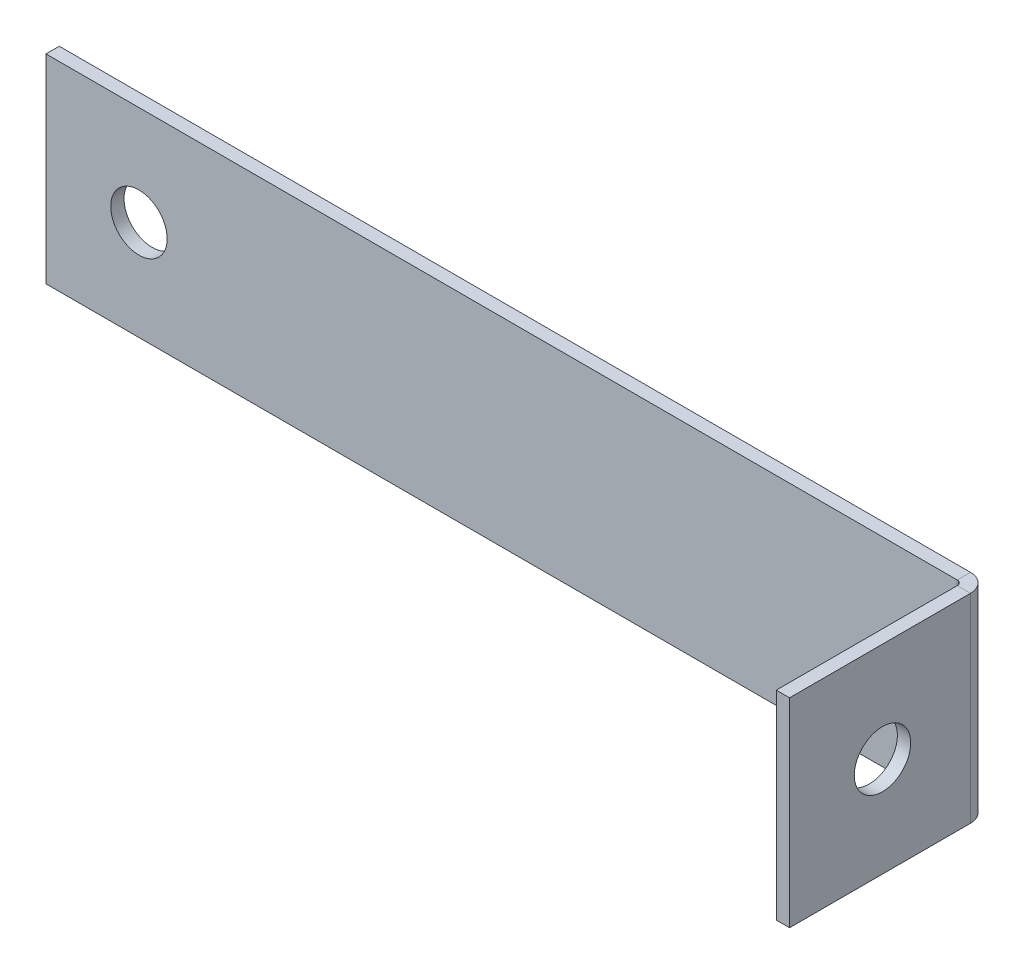
SolidWorks part; units mm, degrees
note: The reader was unsure of these and kept them because the rebuilt part matched: flange length of "Edge-Flange1".
material "Galvanized Steel"
ref_plane "Front Plane" through (0, 0, 0) normal (0, 0, 1) x (1, 0, 0)
ref_plane "Top Plane" through (0, 0, 0) normal (0, 1, 0) x (1, 0, 0)
ref_plane "Right Plane" through (0, 0, 0) normal (1, 0, 0) x (0, 0, -1)
sketch "Sketch1" plane through (0, 0, 0) normal (0, 0, 1) x (1, 0, 0)
  line L1 (60.7597, 25.5212) -> (-79.2403, 25.5212)
  line L2 (60.7597, 25.5212) -> (60.7597, -4.4788)
  line L3 (60.7597, -4.4788) -> (-79.2403, -4.4788)
  line L4 (-79.2403, 25.5212) -> (-79.2403, -4.4788)
  circle A0 centre (-65.2403, 10.5212) radius 4.25
  dimension "D3" = 8.5
  dimension "D1" = 140
  dimension "D2" = 30
  dimension "D4" = 14
base flange "Base-Flange1" sketch "Sketch1" thickness 2 reverse thickness direction no parameters "D1"=0.7366
edge flange "Edge-Flange1" sketch "Sketch8" flange angle 90 flange length 30 flange position material inside bend radius 0.7366 thickness 2 relief obround parameters "D6"=10
sketch "Sketch8" plane through (60.7597, 0, 0) normal (-1, 0, 0) x (0, -1, 0)
  line L1 (4.4788, 0) -> (-25.5212, 0) construction
  line L2 (-25.5212, 0) -> (-25.5212, 28)
  line L3 (-25.5212, 28) -> (4.4788, 28)
  line L4 (4.4788, 28) -> (4.4788, 0)
  line L5 (4.4788, 0) -> (-25.5212, 0)
bend "EdgeBend1" bend radius 0.7366 bend angle 90 parameters "D5"=1
sketch "Sketch9" plane through (60.7597, 0, 0) normal (1, 0, 0) x (0, 0, -1)
  circle A0 centre (-14, 10.5212) radius 4.25
  dimension "D1" = 8.5
extrude "Cut-Extrude1" cut sketch "Sketch9" against normal blind 10 normal cut yes
sketch "Bend-Lines1" [suppressed] plane through (0, 0, 0) normal (0, 1, 0) x (1, 0, 0)
sketch "Bounding-Box1" [suppressed] plane through (0, 0, 0) normal (0, 1, 0) x (1, 0, 0)
sheet metal parameters "Sheet-Metal1" thickness 2 parameters "D1"=0.7366
flat pattern "Flat-Pattern1" [suppressed]
sketch "Bend-Lines2" plane through (0, 0, 0) normal (0, 1, 0) x (1, 0, 0)
sketch3d "Bounding-Box2" [suppressed]
  line L0 (79.2403, -4.4788, 0) -> (-50.7597, -4.4788, 0) construction
  line L1 (79.2403, 25.5212, 0) -> (-50.7597, 25.5212, 0) construction
  line L2 (79.2403, -4.4788, 0) -> (79.2403, 25.5212, 0) construction
  line L3 (-50.7597, -4.4788, 0) -> (-50.7597, 25.5212, 0) construction
sheet metal parameters "Sheet-Metal2" thickness 2 parameters "D1"=0.7366
flat pattern "Flat-Pattern1"
sketch "Bend-Lines2" plane through (0, 0, 0) normal (0, 0, 1) x (1, 0, 0)
  line L0 (49.387, -4.4788) -> (49.387, 25.5212) construction
  line L1 (49.387, -4.4788) -> (49.387, 25.5212) construction
sketch3d "Bounding-Box2" [suppressed]
  line L0 (-79.2403, -4.4788, 0) -> (78.0144, -4.4788, 0) construction
  line L1 (-79.2403, 25.5212, 0) -> (78.0144, 25.5212, 0) construction
  line L2 (-79.2403, -4.4788, 0) -> (-79.2403, 25.5212, 0) construction
  line L3 (78.0144, -4.4788, 0) -> (78.0144, 25.5212, 0) construction
bend of the flat pattern "Flatten-<EdgeBend1>1"
sheet metal parameters "Sheet-Metal3" thickness 2 parameters "D1"=0.7366
flat pattern "Flat-Pattern1"
sketch "Bend-Lines2" plane through (0, 0, 0) normal (0, 0, 1) x (1, 0, 0)
  line L0 (59.387, -4.4788) -> (59.387, 25.5212) construction
  line L1 (59.387, -4.4788) -> (59.387, 25.5212) construction
sketch3d "Bounding-Box2" [suppressed]
  line L0 (-79.2403, -4.4788, 0) -> (88.0144, -4.4788, 0) construction
  line L1 (-79.2403, 25.5212, 0) -> (88.0144, 25.5212, 0) construction
  line L2 (-79.2403, -4.4788, 0) -> (-79.2403, 25.5212, 0) construction
  line L3 (88.0144, -4.4788, 0) -> (88.0144, 25.5212, 0) construction
bend of the flat pattern "Flatten-<EdgeBend1>1"
